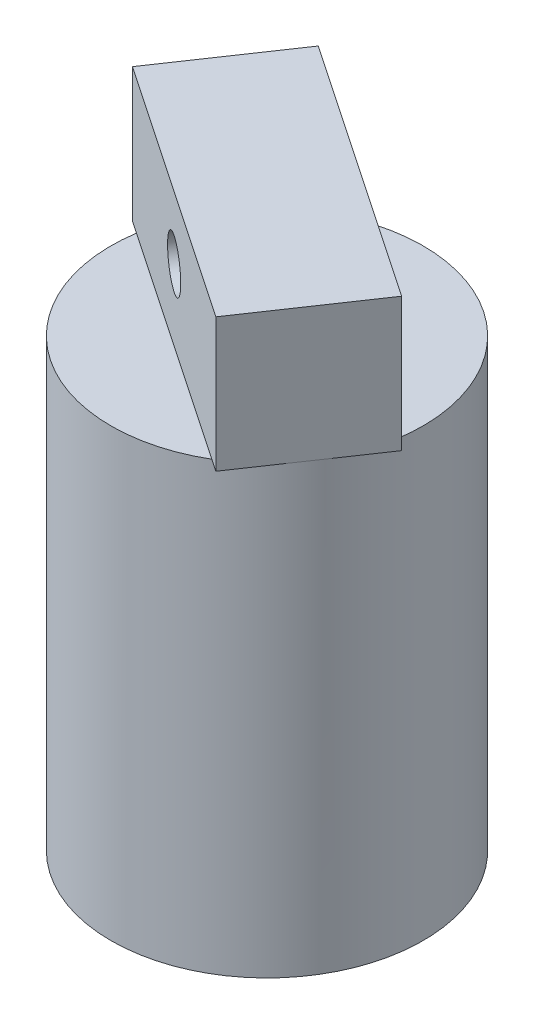
SolidWorks part; units mm, degrees
ref_plane "Спереди" through (0, 0, 0) normal (0, 0, 1) x (1, 0, 0)
ref_plane "Сверху" through (0, 0, 0) normal (0, 1, 0) x (1, 0, 0)
ref_plane "Справа" through (0, 0, 0) normal (1, 0, 0) x (0, 0, -1)
sketch "Эскиз1" plane through (0, 0, 0) normal (0, 1, 0) x (1, 0, 0)
  line L0 (-1.8574, -2.9665) -> (0, 0) construction
  line L1 (0, 0) -> (1.8574, 2.9665) construction
  line L2 (0, 0) -> (2.8979, -1.9627) construction
  line L3 (0, 0) -> (-2.8958, 1.9658) construction
  circle A0 centre (0, 0) radius 3.5
  dimension "D1" = 7
extrude "Бобышка-Вытянуть2" add sketch "Эскиз1" along normal blind 10
sketch "Эскиз2" plane through (0, 0, 0) normal (0, -1, 0) x (1, 0, 0)
  circle A0 centre (0, 0) radius 1.6
  dimension "D1" = 3.2
extrude "Вырез-Вытянуть1" cut sketch "Эскиз2" against normal blind 7
sketch3d "Трехмерный эскиз1"
  line L0 (0, 0, 0) -> (2.8979, 0, 1.9627) construction
  line L1 (2.8979, 10, 1.9627) -> (-2.8979, 10, -1.9627) construction
  line L2 (-2.8979, 10, -1.9627) -> (-2.8979, 11.989, -1.9627)
  line L3 (2.8979, 10, 1.9627) -> (-2.8979, 10, -1.9627)
  line L5 (2.8979, 10, 1.9627) -> (2.8979, 11.989, 1.9627)
  line L6 (2.8979, 11.989, 1.9627) -> (-2.8979, 11.989, -1.9627)
  line L7 (-2.8979, 10, -1.9627) -> (2.8979, 10, 1.9627)
  circle A0 centre (0, 10, 0) radius 3.5 construction
  point P6 (0, 13.5, 0)
sketch "Эскиз3" plane through (0, 0, 0) normal (-0.5608, 0, 0.828) x (0.828, 0, 0.5608)
  line L8 (3.5, 10) -> (-3.5, 10)
  line L9 (3.5, 10) -> (3.5, 13)
  line L10 (3.5, 13) -> (-3.5, 13)
  line L11 (-3.5, 10) -> (-3.5, 13)
  circle A0 centre (0, 11.5977) radius 0.5483
  point P2 (0, 11.5977)
  dimension "D1" = 3
extrude "Бобышка-Вытянуть4" add sketch "Эскиз3" along normal blind 1.5 and the other way blind 1.5
